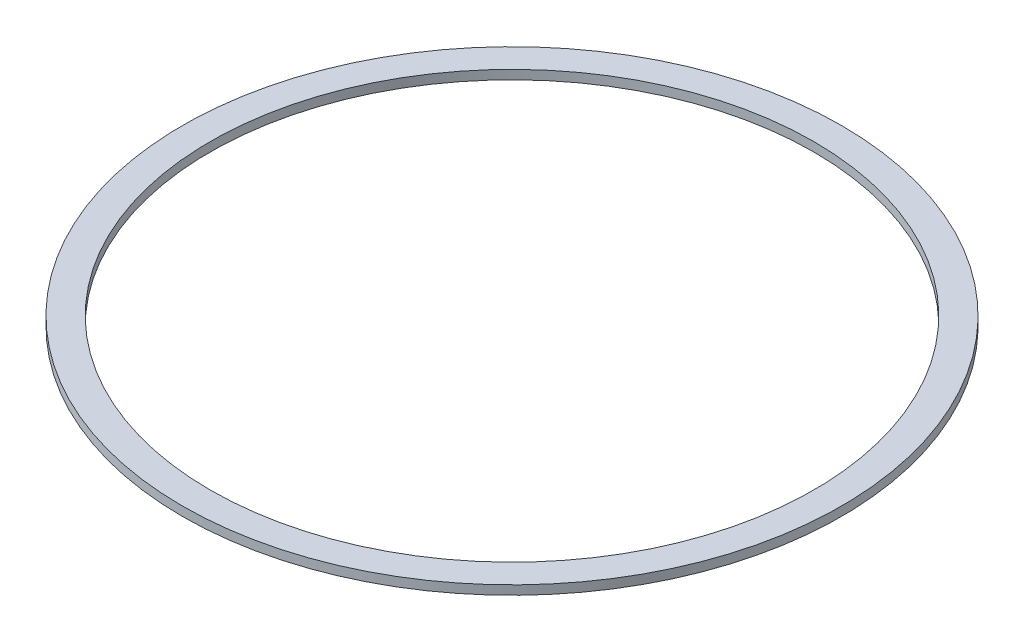
SolidWorks part; units mm, degrees
material "Silicon"
ref_plane "Front Plane" through (0, 0, 0) normal (0, 0, 1) x (1, 0, 0)
ref_plane "Top Plane" through (0, 0, 0) normal (0, 1, 0) x (1, 0, 0)
ref_plane "Right Plane" through (0, 0, 0) normal (1, 0, 0) x (0, 0, -1)
sketch "Sketch1" plane through (0, 0, 0) normal (0, 1, 0) x (1, 0, 0)
  circle A0 centre (0, 0) radius 50
  circle A1 centre (0, 0) radius 54.6
extrude "Boss-Extrude1" add sketch "Sketch1" along normal blind 1.5
